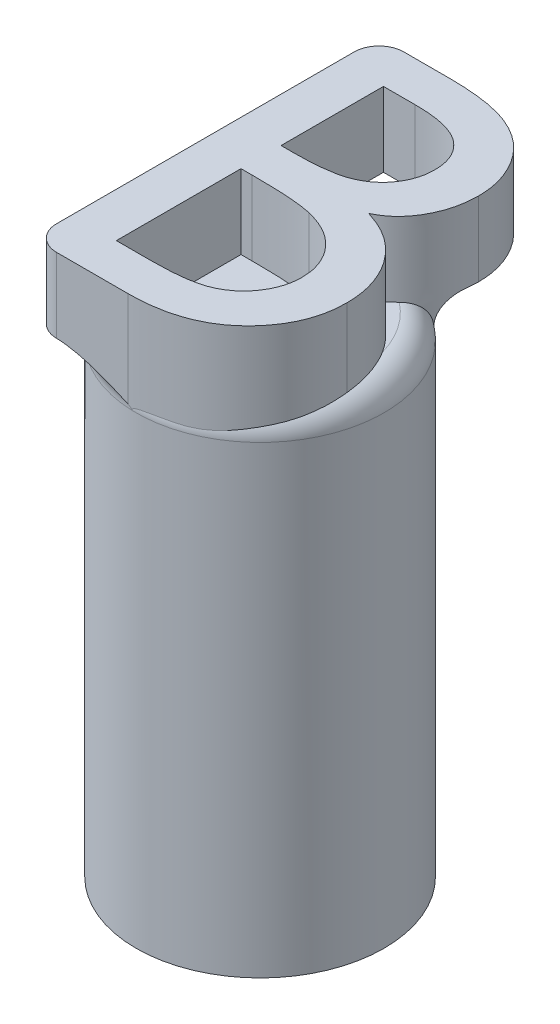
SolidWorks part; units mm, degrees
ref_plane "Ebene vorne" through (0, 0, 0) normal (0, 0, 1) x (1, 0, 0)
ref_plane "Ebene oben" through (0, 0, 0) normal (0, 1, 0) x (1, 0, 0)
ref_plane "Ebene rechts" through (0, 0, 0) normal (1, 0, 0) x (0, 0, -1)
sketch "Skizze1" plane through (0, 0, 0) normal (0, 1, 0) x (1, 0, 0)
  circle A0 centre (0, 0) radius 5
  point P3 (0, 0)
extrude "Aufsatz-Linear austragen2" add sketch "Skizze1" along normal blind 20
sketch "Skizze2" plane through (0, 20, 0) normal (0, 1, 0) x (1, 0, 0)
  circle A1 centre (0, 0) radius 5 construction
  text T0 "<b>B</b>" font "Century Gothic" height 14
  point P5 (-7.3473, 9.0132)
  point P6 (-41.4157, 10.5273)
  dimension "D2" = 6
  dimension "D1" = 5
extrude "Aufsatz-Linear austragen3" add sketch "Skizze2" along normal blind 3
fillet "Verrundung2" radius 1 3 edges at (-0.5376, 20, -4.971) (4.7123, 20, 1.6715) (-5, 20, 0)
fillet "Verrundung3" radius 1 3 edges at (-2.4737, 20, 4.3452) (2.2496, 20, -4.4653) (-3.4122, 20, -3.6547)
fillet "Verrundung4" radius 1 2 edges at (-4.2051, 21.5, -9) (-4.2051, 21.5, 5)
sketch "Skizze3" plane through (0, 0, 0) normal (0, -1, 0) x (-1, 0, 0)
  circle A0 centre (0, 0) radius 4.5
extrude "Schnitt-Linear austragen1" cut sketch "Skizze3" against normal blind 1
chamfer "Fase1" distance 1 angle 31 1 edges at (0, 0, -4.5) first distance on face at (0, 0, -4.5)
sketch "Skizze4" plane through (0, 1, 0) normal (0, -1, 0) x (-1, 0, 0)
  circle A0 centre (0, 0) radius 1.55
extrude "Schnitt-Linear austragen3" cut sketch "Skizze4" against normal blind 18
